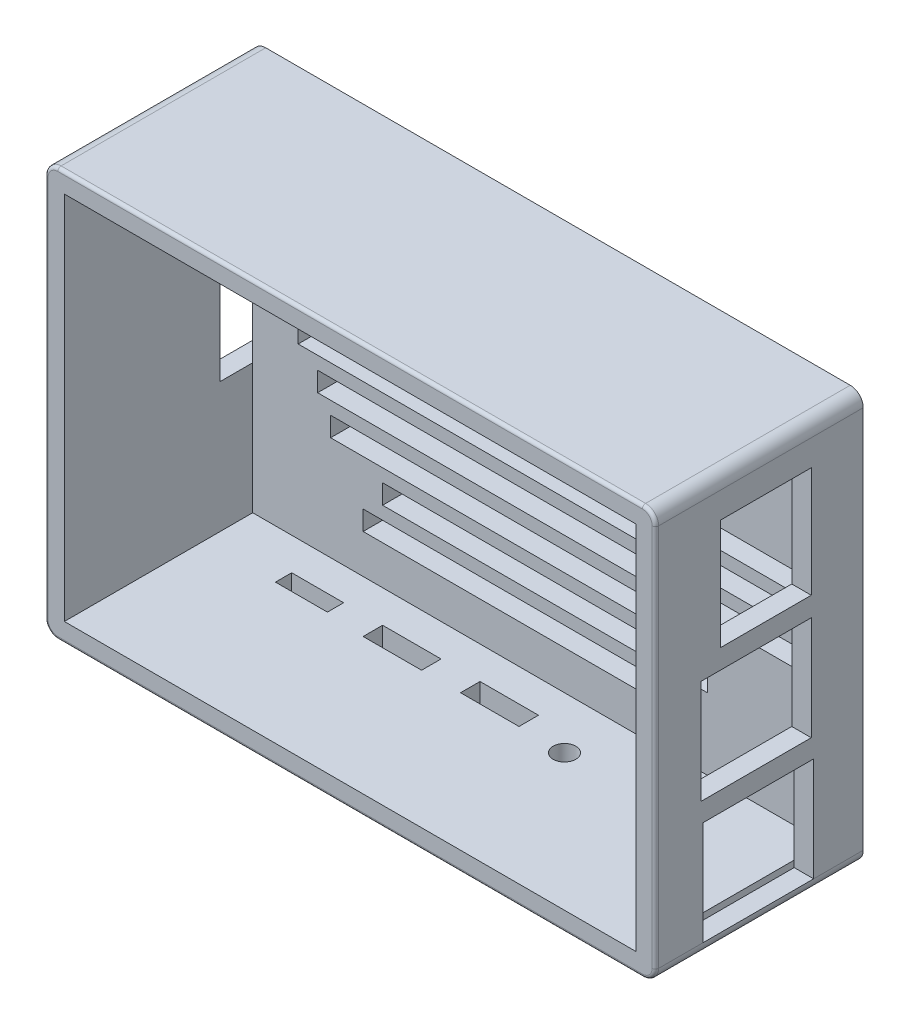
SolidWorks part; units mm, degrees
ref_plane "Front Plane" through (0, 0, 0) normal (0, 0, 1) x (1, 0, 0)
ref_plane "Top Plane" through (0, 0, 0) normal (0, 1, 0) x (1, 0, 0)
ref_plane "Right Plane" through (0, 0, 0) normal (1, 0, 0) x (0, 0, -1)
sketch "Sketch1" plane through (0, 0, 0) normal (0, 0, 1) x (1, 0, 0)
  line L1 (0, 0) -> (94, 0)
  line L2 (0, 0) -> (0, 63)
  line L3 (0, 63) -> (94, 63)
  line L4 (94, 0) -> (94, 63)
  dimension "D1" = 94
  dimension "D2" = 63
extrude "Boss-Extrude1" add sketch "Sketch1" along normal blind 32
shell "Shell1" thickness 3
sketch "Sketch2" plane through (0, 0, 0) normal (-1, 0, 0) x (0, 0, 1)
  line L0 (0, 63) -> (0, 0) construction
  line L1 (8, 40) -> (0, 40)
  line L2 (8, 40) -> (8, 23)
  line L3 (8, 23) -> (0, 23)
  line L4 (0, 40) -> (0, 23)
  line L5 (32, 63) -> (0, 63) construction
  dimension "D1" = 17
  dimension "D2" = 8
  dimension "D3" = 0
  dimension "D4" = 23
extrude "Cut-Extrude1" cut sketch "Sketch2" against normal blind 3
sketch "Sketch3" plane through (94, 0, 0) normal (1, 0, 0) x (0, 0, -1)
  line L0 (-32, 63) -> (0, 63) construction
  line L1 (-22, 40) -> (-8, 40)
  line L2 (-22, 40) -> (-22, 57)
  line L3 (-22, 57) -> (-8, 57)
  line L4 (-8, 40) -> (-8, 57)
  line L5 (0, 0) -> (0, 63) construction
  dimension "D1" = 17
  dimension "D2" = 14
  dimension "D3" = 6
  dimension "D4" = 8
extrude "Cut-Extrude2" cut sketch "Sketch3" against normal blind 3
sketch "Sketch4" plane through (94, 0, 0) normal (1, 0, 0) x (0, 0, -1)
  line L0 (-22, 40) -> (-8, 40) construction
  line L1 (-25, 21) -> (-8, 21)
  line L2 (-25, 21) -> (-25, 37)
  line L3 (-25, 37) -> (-8, 37)
  line L4 (-8, 21) -> (-8, 37)
  line L5 (0, 0) -> (0, 63) construction
  dimension "D1" = 16
  dimension "D2" = 17
  dimension "D3" = 3
  dimension "D4" = 8
extrude "Cut-Extrude4" cut sketch "Sketch4" against normal blind 3
sketch "Sketch5" plane through (94, 0, 0) normal (1, 0, 0) x (0, 0, -1)
  line L0 (-25, 21) -> (-8, 21) construction
  line L1 (-24.6328, 2) -> (-7.6328, 2)
  line L2 (-24.6328, 2) -> (-24.6328, 18)
  line L3 (-24.6328, 18) -> (-7.6328, 18)
  line L4 (-7.6328, 2) -> (-7.6328, 18)
  dimension "D1" = 17
  dimension "D2" = 16
  dimension "D3" = 3
extrude "Cut-Extrude5" cut sketch "Sketch5" against normal blind 3
sketch "Sketch6" plane through (0, 0, 0) normal (0, -1, 0) x (-1, 0, 0)
  line L0 (-94, -32) -> (-94, 0) construction
  line L1 (0, 0) -> (-94, 0) construction
  circle A0 centre (-59, -11) radius 1.75
  dimension "D1" = 3.5
  dimension "D2" = 35
  dimension "D3" = 11
extrude "Cut-Extrude6" cut sketch "Sketch6" against normal blind 3
sketch "Sketch7" plane through (0, 0, 0) normal (0, -1, 0) x (-1, 0, 0)
  line L0 (0, 0) -> (-94, 0) construction
  line L1 (-43, -11) -> (-52, -11)
  line L2 (-43, -11) -> (-43, -8)
  line L3 (-43, -8) -> (-52, -8)
  line L4 (-52, -11) -> (-52, -8)
  line L5 (-28, -11) -> (-37, -11)
  line L6 (-28, -11) -> (-28, -8)
  line L7 (-28, -8) -> (-37, -8)
  line L8 (-37, -11) -> (-37, -8)
  line L9 (-14, -10.5) -> (-22, -10.5)
  line L10 (-14, -10.5) -> (-14, -8)
  line L11 (-14, -8) -> (-22, -8)
  line L12 (-22, -10.5) -> (-22, -8)
  circle A0 centre (-59, -11) radius 1.75 construction
  dimension "D1" = 9
  dimension "D2" = 3
  dimension "D3" = 8
  dimension "D4" = 7
  dimension "D5" = 9
  dimension "D6" = 3
  dimension "D7" = 8
  dimension "D8" = 6
  dimension "D9" = 8
  dimension "D10" = 2.5
  dimension "D11" = 6
  dimension "D12" = 8
extrude "Cut-Extrude7" cut sketch "Sketch7" against normal blind 3
sketch "Sketch9" plane through (0, 0, 32) normal (0, 0, 1) x (1, 0, 0)
  line L0 (77, 60.4844) -> (77, 1.6207) construction
  line L1 (94, 0) -> (94, 63) construction
  text T0 "CanaKit"
  dimension "D1" = 17
extrude "Cut-Extrude8" cut sketch "Sketch9" against normal blind 1
sketch "Sketch11" plane through (0, 0, 0) normal (0, -1, 0) x (1, 0, 0)
  line L0 (-5.7016, 1.5) -> (107.7038, 1.5) construction
  line L1 (0, 0) -> (94, 0) construction
  text T0 "             PWR       HDMI     HDMI    A/V" font "Century Gothic" height in points 10
  dimension "D1" = 1.5
extrude "Cut-Extrude9" cut sketch "Sketch11" against normal blind 1
sketch "Sketch14" plane through (0, 0, 0) normal (0, 0, -1) x (-1, 0, 0)
  line L0 (-94, 63) -> (0, 63) construction
  line L1 (-70, 52) -> (-20, 52)
  line L2 (-70, 52) -> (-70, 49)
  line L3 (-70, 49) -> (-20, 49)
  line L4 (-20, 52) -> (-20, 49)
  line L5 (-94, 0) -> (-94, 63) construction
  line L7 (-73, 47) -> (-23, 47)
  line L8 (-73, 47) -> (-73, 44)
  line L9 (-73, 44) -> (-23, 44)
  line L10 (-23, 47) -> (-23, 44)
  line L11 (-75, 42) -> (-15, 42)
  line L12 (-75, 42) -> (-75, 39)
  line L13 (-75, 39) -> (-15, 39)
  line L14 (-15, 42) -> (-15, 39)
  line L15 (-89, 37) -> (-13, 37)
  line L16 (-89, 37) -> (-89, 34)
  line L17 (-89, 34) -> (-13, 34)
  line L18 (-13, 37) -> (-13, 34)
  line L19 (-86, 32) -> (-10, 32)
  line L20 (-86, 32) -> (-86, 29)
  line L21 (-86, 29) -> (-10, 29)
  line L22 (-10, 32) -> (-10, 29)
  line L23 (-89, 24) -> (-13, 24)
  line L24 (-89, 24) -> (-89, 27)
  line L25 (-89, 27) -> (-13, 27)
  line L26 (-13, 24) -> (-13, 27)
  line L27 (-75, 22) -> (-15, 22)
  line L28 (-75, 22) -> (-75, 19)
  line L29 (-75, 19) -> (-15, 19)
  line L30 (-15, 22) -> (-15, 19)
  line L31 (-73, 17) -> (-23, 17)
  line L32 (-73, 17) -> (-73, 14)
  line L33 (-73, 14) -> (-23, 14)
  line L34 (-23, 17) -> (-23, 14)
  line L35 (-70, 9) -> (-20, 9)
  line L36 (-70, 9) -> (-70, 12)
  line L37 (-70, 12) -> (-20, 12)
  line L38 (-20, 9) -> (-20, 12)
  dimension "D1" = 50
  dimension "D2" = 3
  dimension "D3" = 11
  dimension "D4" = 24
  dimension "D5" = 50
  dimension "D6" = 3
  dimension "D7" = 21
  dimension "D8" = 16
  dimension "D9" = 60
  dimension "D10" = 3
  dimension "D11" = 19
  dimension "D12" = 21
  dimension "D13" = 76
  dimension "D14" = 3
  dimension "D15" = 5
  dimension "D16" = 26
  dimension "D17" = 76
  dimension "D18" = 3
  dimension "D19" = 8
  dimension "D20" = 31
  dimension "D21" = 76
  dimension "D22" = 3
  dimension "D23" = 5
  dimension "D24" = 36
  dimension "D25" = 60
  dimension "D26" = 3
  dimension "D27" = 19
  dimension "D28" = 41
  dimension "D29" = 50
  dimension "D30" = 3
  dimension "D31" = 21
  dimension "D32" = 46
  dimension "D33" = 50
  dimension "D34" = 3
  dimension "D35" = 24
  dimension "D36" = 51
extrude "Cut-Extrude11" cut sketch "Sketch14" against normal blind 10
fillet "Fillet1" radius 2 4 edges at (94, 0, 16) (0, 0, 16) (94, 63, 16) (0, 63, 16)
fillet "Fillet2" radius 0.5 8 edges at (0.5858, 0.5858, 32) (0, 31.5, 32) (0.5858, 62.4142, 32) (47, 63, 32) (93.4142, 62.4142, 32) (94, 31.5, 32) (93.4142, 0.5858, 32) (47, 0, 32)
sketch "Çizim1" plane through (0, 0, 32) normal (0, 0, 1) x (1, 0, 0)
  line L1 (3, 60) -> (91, 60)
  line L2 (3, 60) -> (3, 3)
  line L3 (3, 3) -> (91, 3)
  line L4 (91, 60) -> (91, 3)
extrude "Kes-Ekstrüzyon1" cut sketch "Çizim1" against normal blind 10
